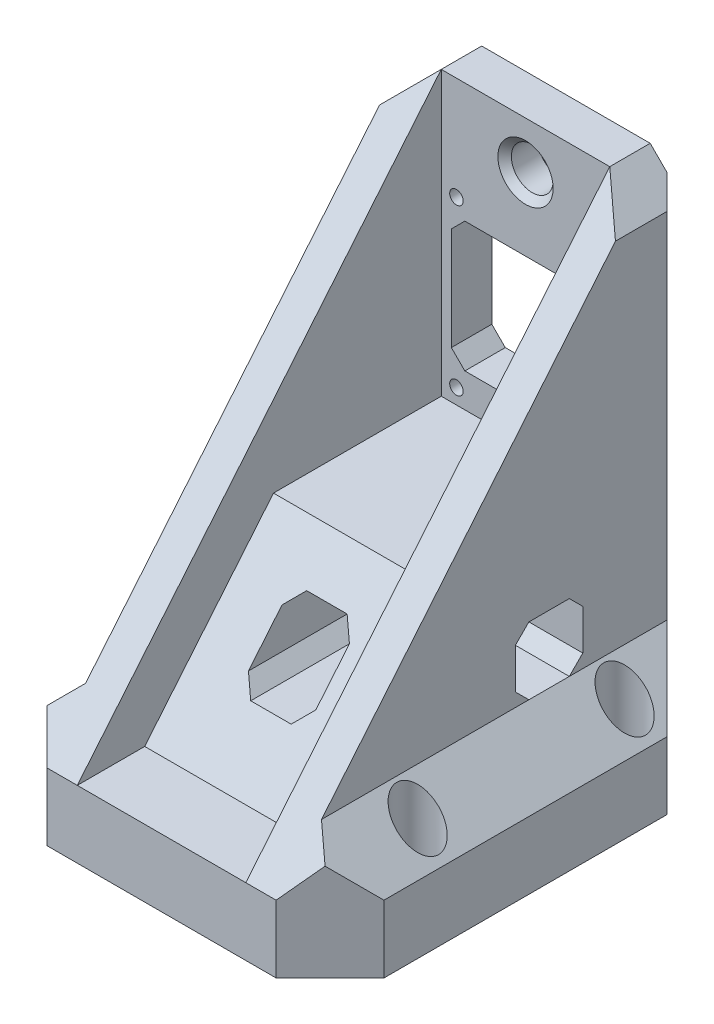
SolidWorks part; units mm, degrees
ref_plane "Front Plane" through (0, 0, 0) normal (0, 0, 1) x (1, 0, 0)
ref_plane "Top Plane" through (0, 0, 0) normal (0, 1, 0) x (1, 0, 0)
ref_plane "Right Plane" through (0, 0, 0) normal (1, 0, 0) x (0, 0, -1)
sketch "Sketch1" plane through (0, 0, 0) normal (0, 1, 0) x (1, 0, 0)
  line L1 (-25, 30) -> (25, 30)
  line L2 (-25, 30) -> (-25, -30)
  line L3 (-25, -30) -> (25, -30)
  line L4 (25, 30) -> (25, -30)
  line L5 (-25, 30) -> (25, -30) construction
  line L6 (-25, -30) -> (25, 30) construction
  point P0 (0, 0)
  dimension "D1" = 50
  dimension "D2" = 60
extrude "Boss-Extrude1" add sketch "Sketch1" along normal blind 10
sketch "Sketch2" plane through (0, 0, 0) normal (0, 1, 0) x (1, 0, 0)
  line L0 (-25, -30) -> (25, -30) construction
  line L1 (-21, -13) -> (21, -13) construction
  line L2 (-21, -13) -> (-21, 17.7) construction
  line L3 (-21, 17.7) -> (21, 17.7) construction
  line L4 (21, -13) -> (21, 17.7) construction
  line L5 (-21, -13) -> (21, 17.7) construction
  line L6 (-21, 17.7) -> (21, -13) construction
  circle A0 centre (-21, 17.7) radius 2
  circle A1 centre (-21, -13) radius 2
  circle A2 centre (21, 17.7) radius 2
  circle A3 centre (21, -13) radius 2
  point P0 (0, 2.35)
  dimension "D4" = 4
  dimension "D1" = 42
  dimension "D2" = 30.7
  dimension "D3" = 17
extrude "Cut-Extrude1" cut sketch "Sketch2" along normal blind 6
sketch "Sketch3" plane through (0, 6, 0) normal (0, -1, 0) x (1, 0, 0)
  circle A0 centre (-21, 13) radius 3.1
  circle A1 centre (21, 13) radius 3.1
  circle A2 centre (21, -17.7) radius 3.1
  circle A3 centre (-21, -17.7) radius 3.1
  dimension "D1" = 6.2
extrude "Cut-Extrude2" cut sketch "Sketch3" against normal up to next
sketch "Sketch5" plane through (0, 10, 0) normal (0, 1, 0) x (1, 0, 0)
  line L0 (25, 30) -> (-25, 30) construction
  line L1 (-12.5, 24) -> (12.5, 24)
  line L2 (-12.5, 24) -> (-12.5, 30)
  line L3 (-12.5, 30) -> (12.5, 30)
  line L4 (12.5, 24) -> (12.5, 30)
  line L5 (-12.5, 24) -> (12.5, 30) construction
  line L6 (-12.5, 30) -> (12.5, 24) construction
  point P0 (0, 27)
  dimension "D1" = 6
  dimension "D2" = 25
extrude "Boss-Extrude3" add sketch "Sketch5" along normal blind 65
sketch "Sketch6" plane through (0, 0, -30) normal (0, 0, -1) x (-1, 0, 0)
  line L1 (-11, 38) -> (11, 38)
  line L2 (-11, 38) -> (-11, 57.25)
  line L3 (-11, 57.25) -> (11, 57.25)
  line L4 (11, 38) -> (11, 57.25)
  line L5 (-11, 38) -> (11, 57.25) construction
  line L6 (-11, 57.25) -> (11, 38) construction
  line L7 (-12.5, 75) -> (12.5, 75) construction
  point P0 (0, 47.625)
  dimension "D1" = 22
  dimension "D2" = 19.25
  dimension "D3" = 17.75
extrude "Cut-Extrude3" cut sketch "Sketch6" against normal up to next
sketch "Sketch7" plane through (0, 0, -24) normal (0, 0, 1) x (1, 0, 0)
  line L1 (-10.25, 35.25) -> (10.25, 35.25) construction
  line L2 (-10.25, 35.25) -> (-10.25, 59.7) construction
  line L3 (-10.25, 59.7) -> (10.25, 59.7) construction
  line L4 (10.25, 35.25) -> (10.25, 59.7) construction
  line L5 (-10.25, 35.25) -> (10.25, 59.7) construction
  line L6 (-10.25, 59.7) -> (10.25, 35.25) construction
  line L7 (-12.5, 75) -> (12.5, 75) construction
  circle A0 centre (10.25, 35.25) radius 1
  circle A1 centre (-10.25, 35.25) radius 1
  circle A2 centre (-10.25, 59.7) radius 1
  circle A3 centre (10.25, 59.7) radius 1
  point P0 (0, 47.475)
  dimension "D4" = 2
  dimension "D1" = 20.5
  dimension "D2" = 24.45
  dimension "D3" = 15.3
extrude "Cut-Extrude4" cut sketch "Sketch7" against normal blind 2.5
sketch "Sketch8" plane through (0, 0, -26.5) normal (0, 0, 1) x (1, 0, 0)
  circle A0 centre (-10.25, 59.7) radius 2
  circle A1 centre (10.25, 59.7) radius 2
  circle A2 centre (10.25, 35.25) radius 2
  circle A3 centre (-10.25, 35.25) radius 2
  dimension "D1" = 4
extrude "Cut-Extrude5" cut sketch "Sketch8" against normal up to next
sketch "Sketch9" plane through (12.5, 0, 0) normal (1, 0, 0) x (0, 0, -1)
  line L0 (30, 75) -> (24, 75)
  line L4 (-30, 10) -> (30, 10)
  line L5 (30, 10) -> (30, 75)
  line L6 (30, 75) -> (30, 10) construction
  line L8 (-30, 10) -> (24, 75)
extrude "Boss-Extrude4" add sketch "Sketch9" along normal blind 5
mirror "Mirror1" about plane through (0, 0, 0) normal (1, 0, 0) of "Boss-Extrude4"
chamfer "Chamfer1" distance 7.5 angle 45 2 edges at (17.5, 10, 0) (-17.5, 10, 0)
chamfer "Chamfer2" distance 10 angle 45 2 edges at (-25, 5, -30) (25, 5, -30)
chamfer "Chamfer4" distance 5.5 angle 45 1 edges at (0, 0, -30)
chamfer "Chamfer5" distance 5 angle 45 2 edges at (17.5, 75, -25.75) (-17.5, 75, -25.75)
chamfer "Chamfer7" distance 2 angle 45 4 edges at (-11, 57.25, -27) (-11, 38, -27) (11, 38, -27) (11, 57.25, -27)
sketch "Sketch10" plane through (0, 0, -30) normal (0, 0, -1) x (-1, 0, 0)
  circle A0 centre (0, 68) radius 3.1
  circle A1 centre (-10.25, 59.7) radius 2 construction
  dimension "D1" = 6.2
  dimension "D2" = 8.3
extrude "Cut-Extrude6" cut sketch "Sketch10" against normal up to next
chamfer "Chamfer8" distance 1 angle 45 2 edges at (-3.1, 68, -24) (-3.1, 68, -30)
sketch "Sketch11" plane through (-12.5, 0, 0) normal (1, 0, 0) x (0, 0, -1)
  line L0 (-20, 10) -> (24, 10)
  line L1 (24, 10) -> (24, 33)
  line L2 (24, 75) -> (24, 10) construction
  line L3 (24, 33) -> (-0.8923, 33)
  line L4 (30, 38) -> (24, 38) construction
  line L5 (-0.8923, 33) -> (-20, 10)
  line L7 (19.8462, 70) -> (-23.7692, 17.5) construction
  line L9 (-30, 10) -> (20, 10) construction
  dimension "D1" = 5
  dimension "D2" = 10
extrude "Boss-Extrude5" add sketch "Sketch11" along normal up to next
chamfer "Chamfer9" distance 8 angle 45 2 edges at (-25, 5, 30) (25, 5, 30)
sketch "Sketch12" plane through (0, 0, -30) normal (0, 0, -1) x (-1, 0, 0)
  line L1 (-5, 17.5) -> (5, 17.5)
  line L2 (-5, 17.5) -> (-5, 27.5)
  line L3 (-5, 27.5) -> (5, 27.5)
  line L4 (5, 17.5) -> (5, 27.5)
  line L5 (-5, 17.5) -> (5, 27.5) construction
  line L6 (-5, 27.5) -> (5, 17.5) construction
  point P0 (0, 22.5)
  dimension "D1" = 10
extrude "Cut-Extrude7" cut sketch "Sketch12" against normal up to next contours L2 L3 L4 L1
sketch "Sketch14" plane through (-5, 0, 0) normal (1, 0, 0) x (0, 0, -1)
  line L0 (-13.7692, 17.5) -> (30, 17.5) construction
  line L5 (30, 17.5) -> (30, 27.5) construction
  line L6 (-5.4615, 27.5) -> (30, 27.5) construction
  line L7 (5, 17.5) -> (15, 17.5)
  line L8 (5, 17.5) -> (5, 27.5)
  line L9 (5, 27.5) -> (15, 27.5)
  line L10 (15, 17.5) -> (15, 27.5)
  line L11 (5, 17.5) -> (15, 27.5) construction
  line L12 (5, 27.5) -> (15, 17.5) construction
  point P0 (10, 22.5)
  dimension "D1" = 20
extrude "Cut-Extrude9" cut sketch "Sketch14" against normal up to next
mirror "Mirror2" about plane through (0, 0, 0) normal (1, 0, 0) of "Cut-Extrude9"
chamfer "Chamfer11" distance 2 angle 45 20 edges at (11.25, 27.5, -15) (5, 27.5, -22.5) (5, 22.5, -15) (11.25, 17.5, -15) (5, 17.5, -22.5) (-11.25, 17.5, -15) (-5, 17.5, -22.5) (-5, 22.5, -15) (-11.25, 27.5, -15) (-5, 27.5, -22.5) (11.25, 17.5, -5) (5, 17.5, 4.3846) (5, 22.5, -5) (11.25, 27.5, -5) (5, 27.5, 0.2308) (-11.25, 17.5, -5) (-5, 17.5, 4.3846) (-5, 22.5, -5) (-11.25, 27.5, -5) (-5, 27.5, 0.2308)
